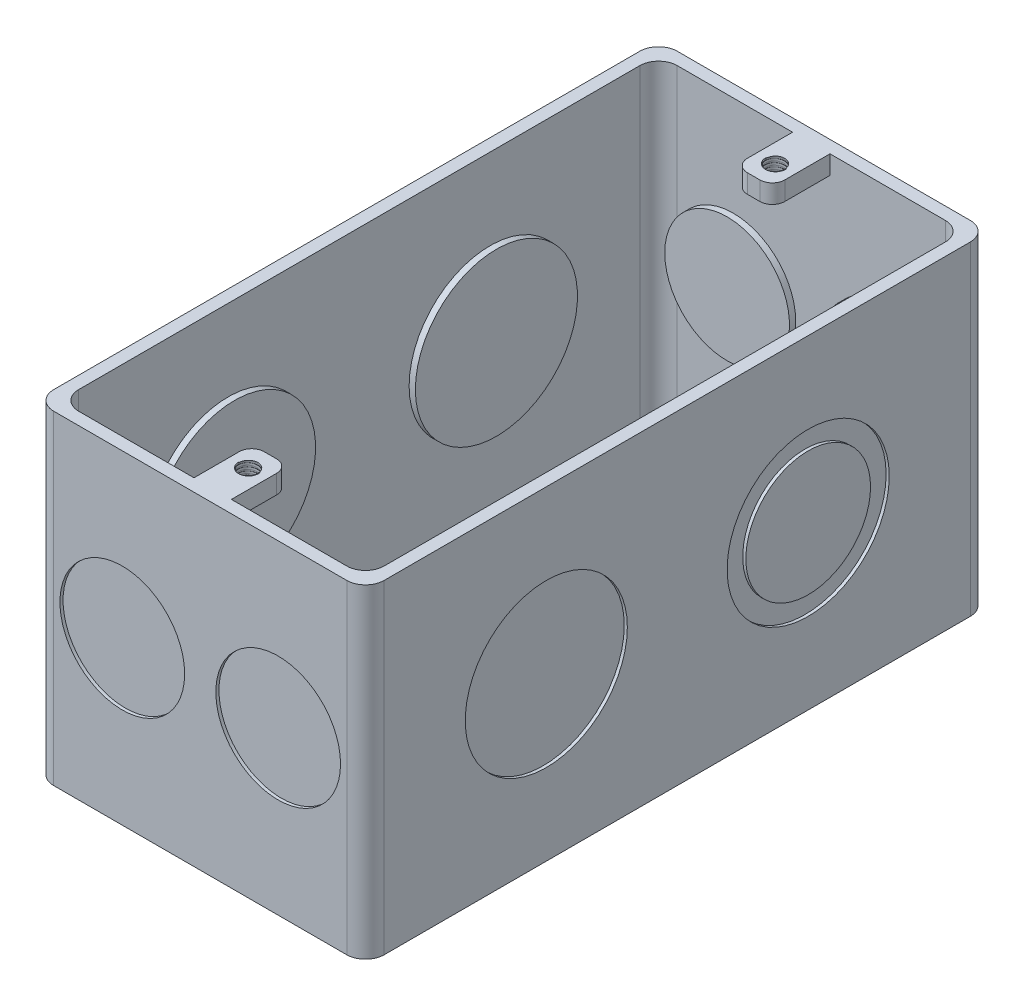
SolidWorks part; units mm, degrees
material "201 Acero inoxidable recocido (SS)"
ref_plane "Alzado" through (0, 0, 0) normal (0, 0, 1) x (1, 0, 0)
ref_plane "Planta" through (0, 0, 0) normal (0, 1, 0) x (1, 0, 0)
ref_plane "Vista lateral" through (0, 0, 0) normal (1, 0, 0) x (0, 0, -1)
sketch "Croquis1" plane through (0, 0, 0) normal (0, 1, 0) x (1, 0, 0)
  line L1 (-26.5, 50) -> (26.5, 50)
  line L2 (-26.5, 50) -> (-26.5, -50)
  line L3 (-26.5, -50) -> (26.5, -50)
  line L4 (26.5, 50) -> (26.5, -50)
  line L5 (-26.5, 50) -> (26.5, -50) construction
  line L6 (-26.5, -50) -> (26.5, 50) construction
  point P0 (0, 0)
  dimension "D1" = 100
  dimension "D2" = 53
extrude "Saliente-Extruir5" add sketch "Croquis1" along normal blind 52
sketch "Croquis6" plane through (0, 52, 0) normal (0, 1, 0) x (1, 0, 0)
  line L0 (-26.5, 50) -> (-26.5, -50) construction
  line L1 (-24.5, 48) -> (24.5, 48)
  line L2 (-24.5, 48) -> (-24.5, -48)
  line L3 (-24.5, -48) -> (24.5, -48)
  line L4 (24.5, 48) -> (24.5, -48)
  line L5 (-24.5, 48) -> (24.5, -48) construction
  line L6 (-24.5, -48) -> (24.5, 48) construction
  line L7 (-26.5, -50) -> (26.5, -50) construction
  point P0 (0, 0)
  dimension "D1" = 2
  dimension "D2" = 2
extrude "Cortar-Extruir4" cut sketch "Croquis6" against normal blind 50
sketch "Croquis7" plane through (0, 52, 0) normal (0, 1, 0) x (1, 0, 0)
  line L0 (24.5, 48) -> (-24.5, 48) construction
  line L2 (0, 0) -> (-59.8241, 0)
  line L3 (-3, 48) -> (3, 48)
  line L4 (-3, 48) -> (-3, 38.75)
  line L5 (-3, 38.75) -> (3, 38.75)
  line L6 (3, 48) -> (3, 38.75)
  line L7 (-3, 48) -> (3, 38.75) construction
  line L8 (-3, 38.75) -> (3, 48) construction
  line L9 (-3, -38.75) -> (3, -48) construction
  line L10 (-3, -48) -> (3, -38.75) construction
  line L11 (3, -48) -> (3, -38.75)
  line L12 (-3, -38.75) -> (3, -38.75)
  line L13 (-3, -48) -> (-3, -38.75)
  line L14 (-3, -48) -> (3, -48)
  line L15 (0, -48) -> (0, -40)
  point P5 (0, 43.375)
  point P18 (0, -43.375)
  dimension "D1" = 6
  dimension "D2" = 9.25
  dimension "D3" = 0
extrude "Saliente-Extruir11" add sketch "Croquis7" against normal blind 3
sketch "Croquis8" plane through (0, 52, 0) normal (0, 1, 0) x (1, 0, 0)
  line L0 (0, 0) -> (-38.2516, 0)
  line L1 (-3, 38.75) -> (3, 38.75) construction
  circle A0 centre (0, 42.25) radius 2
  circle A1 centre (0, -42.25) radius 2
  dimension "D1" = 3.5
extrude "Cortar-Extruir8" cut sketch "Croquis8" against normal blind 3 contours A0 | A1
fillet "Redondeo1" radius 2 1 edges at (-3, 50.5, 38.75)
fillet "Redondeo2" radius 2 1 edges at (3, 50.5, 38.75)
fillet "Redondeo3" radius 2 2 edges at (-3, 50.5, -38.75) (3, 50.5, -38.75)
fillet "Redondeo5" radius 3 1 edges at (-26.5, 26, -50)
fillet "Redondeo6" radius 3 1 edges at (-24.5, 27, -48)
fillet "Redondeo7" radius 3 6 edges at (26.5, 26, 50) (24.5, 27, 48) (-24.5, 27, 48) (-26.5, 26, 50) (24.5, 27, -48) (26.5, 26, -50)
sketch "Croquis9" plane through (-26.5, 0, 0) normal (-1, 0, 0) x (0, 0, 1)
  line L0 (0, 52) -> (0, 0)
  line L1 (-47, 52) -> (47, 52) construction
  line L2 (0, 26) -> (21, 26)
  line L3 (0, 26) -> (-21, 26)
  line L5 (34, 26) -> (34, 9.5642)
  line L6 (50, 52) -> (50, 0) construction
  line L7 (-34, 26) -> (-34, -4.0402)
  line L8 (-50, 0) -> (-50, 52) construction
  circle A0 centre (21, 26) radius 13
  circle A1 centre (-21, 26) radius 13
  dimension "D1" = 42
  dimension "D2" = 16
  dimension "D3" = 16
extrude "Cortar-Extruir9" cut sketch "Croquis9" against normal blind 0.5
sketch "Croquis10" plane through (-26, 0, 0) normal (-1, 0, 0) x (0, 0, 1)
  circle A0 centre (21, 26) radius 13
  circle A1 centre (-21, 26) radius 13
extrude "Saliente-Extruir12" add sketch "Croquis10" against normal blind 2.5
sketch "Croquis11" plane through (-26.5, 0, 0) normal (-1, 0, 0) x (0, 0, 1)
  circle A0 centre (21, 26) radius 10
extrude "Saliente-Extruir14" add sketch "Croquis11" against normal blind 0.5
sketch "Croquis12" plane through (26.5, 0, 0) normal (1, 0, 0) x (0, 0, -1)
  line L0 (0, 52) -> (0, 0)
  line L1 (-47, 52) -> (47, 52) construction
  line L2 (0, 26) -> (21, 26)
  line L3 (0, 26) -> (-21, 26)
  line L4 (-34, 26) -> (-34, -10.9324)
  line L5 (34, 26) -> (34, -10.2375)
  line L6 (-50, 0) -> (-50, 52) construction
  line L7 (50, 52) -> (50, 0) construction
  circle A0 centre (21, 26) radius 13
  circle A1 centre (-21, 26) radius 13
  dimension "D1" = 42
  dimension "D2" = 16
  dimension "D3" = 16
extrude "Cortar-Extruir10" cut sketch "Croquis12" against normal blind 0.5
sketch "Croquis13" plane through (26, 0, 0) normal (1, 0, 0) x (0, 0, -1)
  circle A0 centre (21, 26) radius 13
  circle A1 centre (-21, 26) radius 13
extrude "Saliente-Extruir15" add sketch "Croquis13" against normal blind 2.5
sketch "Croquis14" plane through (26, 0, 0) normal (1, 0, 0) x (0, 0, -1)
  circle A0 centre (21, 26) radius 10
extrude "Saliente-Extruir16" add sketch "Croquis14" along normal blind 0.5
sketch "Croquis15" plane through (0, 0, 50) normal (0, 0, 1) x (1, 0, 0)
  line L0 (0, 52) -> (0, 0)
  line L1 (-23.5, 52) -> (23.5, 52) construction
  line L2 (0, 26) -> (-12.5, 26)
  line L3 (0, 26) -> (12.5, 26)
  line L4 (-2.5, 26) -> (-2.5, 16.7258)
  line L5 (2.5, 26) -> (2.5, 16.1819)
  circle A0 centre (-12.5, 26) radius 10
  circle A1 centre (12.5, 26) radius 10
  dimension "D1" = 5
  dimension "D2" = 2.5
extrude "Cortar-Extruir12" cut sketch "Croquis15" against normal blind 0.5
sketch "Croquis16" plane through (0, 0, 49.5) normal (0, 0, 1) x (1, 0, 0)
  circle A0 centre (-12.5, 26) radius 10
  circle A1 centre (12.5, 26) radius 10
extrude "Saliente-Extruir18" add sketch "Croquis16" against normal blind 2.5
sketch "Croquis17" plane through (0, 0, -50) normal (0, 0, -1) x (-1, 0, 0)
  line L0 (0, 52) -> (0, 0)
  line L1 (-23.5, 52) -> (23.5, 52) construction
  line L2 (0, 26) -> (-12.5, 26)
  line L3 (0, 26) -> (12.5, 26)
  line L4 (2.5, 26) -> (2.5, 15.5729)
  line L5 (-2.5, 26) -> (-2.5, 14.7653)
  circle A0 centre (-12.5, 26) radius 10
  circle A1 centre (12.5, 26) radius 10
  dimension "D1" = 5
  dimension "D2" = 2.5
extrude "Cortar-Extruir13" cut sketch "Croquis17" against normal blind 0.5
sketch "Croquis18" plane through (0, 0, -49.5) normal (0, 0, -1) x (-1, 0, 0)
  circle A0 centre (-12.5, 26) radius 10
  circle A1 centre (12.5, 26) radius 10
extrude "Saliente-Extruir19" add sketch "Croquis18" against normal blind 2.5
sketch "Croquis19" plane through (0, 0, 0) normal (0, -1, 0) x (1, 0, 0)
  line L0 (0, 50) -> (0, -50)
  line L1 (-23.5, 50) -> (23.5, 50) construction
  line L2 (23.5, -50) -> (-23.5, -50) construction
  line L3 (-26.5, 0) -> (26.5, 0)
  line L4 (-26.5, -47) -> (-26.5, 47) construction
  line L5 (26.5, 47) -> (26.5, -47) construction
  line L6 (0, -5) -> (-14.0188, -5)
  line L7 (0, 5) -> (-8.8113, 5)
  circle A0 centre (0, 19) radius 14
  circle A1 centre (0, -19) radius 14
  dimension "D1" = 10
  dimension "D2" = 5
extrude "Cortar-Extruir14" cut sketch "Croquis19" against normal blind 0.5 contours L0 A0 | L0 A0 | L0 A1 | L0 A1
sketch "Croquis20" plane through (0, 0.5, 0) normal (0, -1, 0) x (1, 0, 0)
  circle A0 centre (0, 19) radius 14
  circle A1 centre (0, -19) radius 14
extrude "Saliente-Extruir20" add sketch "Croquis20" against normal blind 2.5
sketch "Croquis21" plane through (0, 0, 0) normal (0, -1, 0) x (1, 0, 0)
  line L0 (0, 50) -> (0, -37.8945)
  line L1 (-23.5, 50) -> (23.5, 50) construction
  line L2 (-26.5, 0) -> (9.1947, 0)
  line L3 (-26.5, -47) -> (-26.5, 47) construction
  line L4 (26.5, 47) -> (26.5, -47) construction
  circle A0 centre (13.5, 37) radius 3
  circle A2 centre (-13.5, -37) radius 3
  dimension "D1" = 13
  dimension "D2" = 13
extrude "Cortar-Extruir15" cut sketch "Croquis21" against normal blind 25 contours A2 | A0
sketch "Croquis22" plane through (0, 0, 0) normal (0, -1, 0) x (1, 0, 0)
  line L0 (13.5, 37) -> (13.5, 30.0356)
  line L1 (13.5, -37) -> (13.5, -40.7009)
  circle A0 centre (13.5, -37) radius 1.5
  dimension "D1" = 0
extrude "Cortar-Extruir16" cut sketch "Croquis22" against normal blind 25
sketch "Croquis24" plane through (0, 52, 0) normal (0, 1, 0) x (1, 0, 0)
  circle A0 centre (0, 42.25) radius 2
curve "Hélice/Espiral2" pitch 0.5 height 3 turns 6
sketch "Croquis25" plane through (0, 0, 0) normal (1, 0, 0) x (0, 0, -1)
  line L1 (40.45, 52) -> (40.15, 52.1732)
  line L2 (40.15, 52.1732) -> (40.15, 51.8268)
  line L3 (40.15, 51.8268) -> (40.45, 52)
  circle A0 centre (40.25, 52) radius 0.1 construction
sweep "Cortar-Barrer1" cut profiles "Croquis25" path "Hélice/Espiral2"
sketch "Croquis26" plane through (0, 52, 0) normal (0, 1, 0) x (1, 0, 0)
  circle A0 centre (0, -42.25) radius 2
curve "Hélice/Espiral3" pitch 0.5 height 3 turns 6
sketch "Croquis27" plane through (0, 0, 0) normal (1, 0, 0) x (0, 0, -1)
  line L1 (-44.05, 52) -> (-44.35, 52.1732)
  line L2 (-44.35, 52.1732) -> (-44.35, 51.8268)
  line L3 (-44.35, 51.8268) -> (-44.05, 52)
  circle A0 centre (-44.25, 52) radius 0.1 construction
sweep "Cortar-Barrer2" cut profiles "Croquis27" path "Hélice/Espiral3"
sketch "Croquis28" plane through (0, 52, 0) normal (0, 1, 0) x (1, 0, 0)
  circle A0 centre (0, 42.25) radius 2.3538
  circle A1 centre (0, -42.25) radius 2.788
extrude "Saliente-Extruir21" add sketch "Croquis28" against normal blind 3
sketch "Croquis29" plane through (0, 52, 0) normal (0, 1, 0) x (1, 0, 0)
  line L0 (0, 38.75) -> (0, 42.25)
  line L1 (-1, 38.75) -> (1, 38.75) construction
  line L2 (0, 0) -> (8.9972, 0)
  circle A0 centre (0, 42.25) radius 1.5
  circle A1 centre (0, -42.25) radius 1.5
  dimension "D1" = 3
extrude "Cortar-Extruir21" cut sketch "Croquis29" against normal blind 3
sketch "Croquis31" plane through (0, 52, 0) normal (0, 1, 0) x (1, 0, 0)
  circle A0 centre (0, 42.25) radius 1.5
curve "Hélice/Espiral4" pitch 0.5833 height 3.5 turns 6
sketch "Croquis32" plane through (0, 0, 0) normal (1, 0, 0) x (0, 0, -1)
  line L1 (40.95, 52) -> (40.65, 52.1732)
  line L2 (40.65, 52.1732) -> (40.65, 51.8268)
  line L3 (40.65, 51.8268) -> (40.95, 52)
  circle A0 centre (40.75, 52) radius 0.1 construction
sweep "Cortar-Barrer3" cut profiles "Croquis32" path "Hélice/Espiral4"
sketch "Croquis33" plane through (0, 52, 0) normal (0, 1, 0) x (1, 0, 0)
  circle A0 centre (0, -42.25) radius 1.5
curve "Hélice/Espiral5" pitch 0.5833 height 3.5 turns 6
sketch "Croquis34" plane through (0, 0, 0) normal (1, 0, 0) x (0, 0, -1)
  line L1 (-43.55, 52) -> (-43.85, 52.1732)
  line L2 (-43.85, 52.1732) -> (-43.85, 51.8268)
  line L3 (-43.85, 51.8268) -> (-43.55, 52)
  circle A0 centre (-43.75, 52) radius 0.1 construction
sweep "Cortar-Barrer4" cut profiles "Croquis34" path "Hélice/Espiral5"
